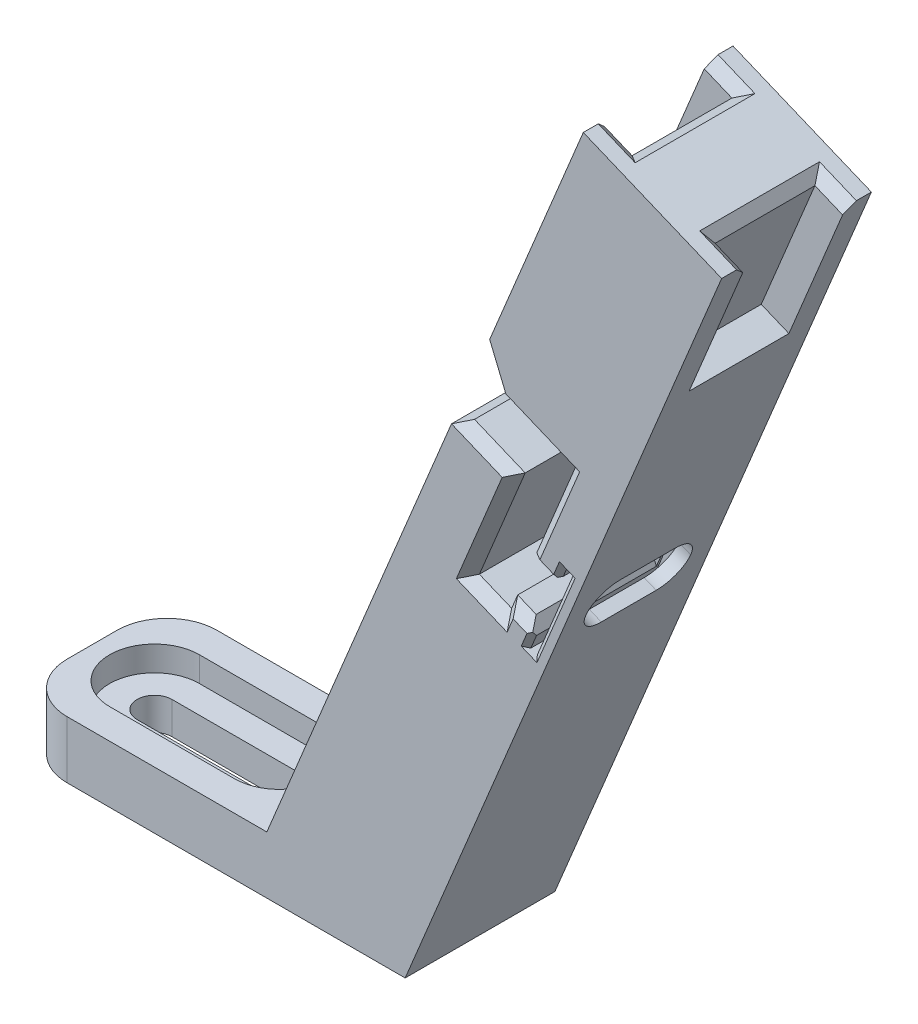
SolidWorks part; units mm, degrees
ref_plane "Front Plane" through (0, 0, 0) normal (0, 0, 1) x (1, 0, 0)
ref_plane "Top Plane" through (0, 0, 0) normal (0, 1, 0) x (1, 0, 0)
ref_plane "Right Plane" through (0, 0, 0) normal (1, 0, 0) x (0, 0, -1)
sketch "Sketch1" plane through (0, 0, 0) normal (0, 0, 1) x (1, 0, 0)
  line L7 (0, 216.4784) -> (-153.0734, 153.0734)
  line L8 (-153.0734, 153.0734) -> (-216.4784, 0)
  line L10 (0, 248.9502) -> (-176.0344, 176.0344)
  line L11 (-176.0344, 176.0344) -> (-244.1948, 11.4805)
  line L12 (0, 248.9502) -> (0, 216.4784)
  line L14 (-244.1948, 11.4805) -> (-244.1948, 0)
  line L15 (-244.1948, 0) -> (-216.4784, 0)
  line L18 (0, 0) -> (-212.4923, 88.0172) construction
  line L20 (0, 0) -> (-88.0172, 212.4923) construction
  line L27 (0, 248.9502) -> (-176.0344, 176.0344) construction
  line L28 (0, 216.4784) -> (-153.0734, 153.0734) construction
  line L29 (153.0734, 153.0734) -> (0, 216.4784) construction
  line L30 (176.0344, 176.0344) -> (0, 248.9502) construction
  line L31 (153.0734, 153.0734) -> (76.5367, 184.7759) [skipped]
  line L32 (216.4784, 0) -> (153.0734, 153.0734) construction
  line L33 (244.1948, 11.4805) -> (176.0344, 176.0344) construction
  line L34 (216.4784, 0) -> (184.7759, 76.5367) [skipped]
  line L35 (153.0734, -153.0734) -> (184.7759, -76.5367) [skipped]
  line L36 (0, -216.4784) -> (76.5367, -184.7759) [skipped]
  line L37 (-153.0734, -153.0734) -> (-76.5367, -184.7759) [skipped]
  line L38 (-216.4784, 0) -> (-184.7759, -76.5367) [skipped]
  dimension "D3" = 30
  dimension "D2" = 30
extrude "Boss-Extrude1" add sketch "Sketch1" along normal blind 30
sketch "Sketch3" plane through (0, 0, 30) normal (0, 0, 1) x (1, 0, 0)
  line L0 (-176.0344, 176.0344) -> (-153.0734, 153.0734) construction
  line L1 (0, 232.7143) -> (-164.5539, 164.5539) construction
  line L2 (0, 216.4784) -> (0, 248.9502) construction
  line L3 (-244.1948, 11.4805) -> (-216.4784, 0) construction
  line L4 (-164.5539, 164.5539) -> (-230.3366, 5.7403) construction
  line L5 (-82.2769, 198.6341) -> (-76.5367, 184.7759) construction
  line L6 (-153.0734, 153.0734) -> (0, 216.4784) construction
  line L7 (-186.6893, 71.9173) -> (-182.8625, 81.1561)
  line L8 (-184.7759, 76.5367) -> (-198.6341, 82.2769) construction
  line L9 (-216.4784, 0) -> (-153.0734, 153.0734) construction
  line L10 (-182.8625, 81.1561) -> (-192.1013, 84.9829)
  line L12 (-195.9281, 75.7441) -> (-186.6893, 71.9173)
  line L13 (-81.1561, 182.8625) -> (-71.9173, 186.6893)
  line L14 (-71.9173, 186.6893) -> (-75.7441, 195.9281)
  line L16 (-84.9829, 192.1013) -> (-81.1561, 182.8625)
  line L17 (-75.7441, 195.9281) -> (-72.8154, 197.1412)
  line L18 (-72.8154, 197.1412) -> (-75.4942, 203.6084)
  line L19 (-75.4942, 203.6084) -> (-97.6673, 194.424)
  line L20 (-106.9061, 190.5971) -> (-104.2273, 184.13)
  line L21 (-104.2273, 184.13) -> (-84.9829, 192.1013)
  line L22 (-106.9061, 190.5971) -> (-111.881, 202.6076)
  line L23 (0, 248.9502) -> (-176.0344, 176.0344) construction
  line L24 (-97.6673, 194.424) -> (-102.6422, 206.4344)
  line L25 (-102.6422, 206.4344) -> (-111.881, 202.6076)
  line L26 (-192.1013, 84.9829) -> (-184.13, 104.2273)
  line L27 (-184.13, 104.2273) -> (-202.6076, 111.881)
  line L28 (-176.0344, 176.0344) -> (-244.1948, 11.4805) construction
  line L29 (-202.6076, 111.881) -> (-206.4344, 102.6422)
  line L30 (-206.4344, 102.6422) -> (-194.424, 97.6673)
  line L31 (-194.424, 97.6673) -> (-203.6084, 75.4942)
  line L32 (-203.6084, 75.4942) -> (-197.1412, 72.8154)
  line L33 (-197.1412, 72.8154) -> (-195.9281, 75.7441)
  point P24 (-184.7759, 76.5367)
  dimension "D1" = 5
  dimension "D2" = 5
  dimension "D3" = 10
  dimension "D4" = 5
  dimension "D5" = 5
  dimension "D6" = 10
  dimension "D7" = 3.17
  dimension "D8" = 7
  dimension "D9" = 34
  dimension "D10" = 10
  dimension "D11" = 3.17
  dimension "D12" = 34
  dimension "D13" = 7
  dimension "D14" = 10
  dimension "D15" = 10
  dimension "D16" = 10
sketch "Sketch4" plane through (-244.1948, 0, 0) normal (-1, 0, 0) x (0, 0, 1)
  line L1 (0, 0) -> (30, 0)
  line L2 (0, 0) -> (0, 11.4805)
  line L3 (0, 11.4805) -> (30, 11.4805)
  line L4 (30, 0) -> (30, 11.4805)
extrude "Boss-Extrude2" add sketch "Sketch4" along normal blind 50
sketch "Sketch5" plane through (0, 11.4805, 0) normal (0, 1, 0) x (1, 0, 0)
  line L0 (-244.1948, -15) -> (-294.1948, -15) construction
  line L1 (-244.1948, -30) -> (-244.1948, 0) construction
  line L2 (-294.1948, -30) -> (-294.1948, 0) construction
  line L3 (-269.1948, -15) -> (-269.1948, 0) construction
  line L4 (-294.1948, 0) -> (-244.1948, 0) construction
  line L5 (-281.6948, -7.5) -> (-294.1948, -7.5) construction
  line L6 (-281.6948, -7.5) -> (-281.6948, -30) construction
  line L7 (-294.1948, -30) -> (-244.1948, -30) construction
  line L8 (-256.6948, -7.5) -> (-244.1948, -7.5) construction
  line L9 (-256.6948, -7.5) -> (-256.6948, -30) construction
  line L12 (-281.6948, -6) -> (-256.6948, -6)
  line L13 (-281.6948, -24) -> (-256.6948, -24)
  arc A2 (-256.6948, -24) -> (-256.6948, -6) centre (-256.6948, -15) ccw
  arc A3 (-281.6948, -6) -> (-281.6948, -24) centre (-281.6948, -15) ccw
extrude "Cut-Extrude1" cut sketch "Sketch5" against normal blind 5
sketch "Sketch7" plane through (0, 6.4805, 0) normal (0, 1, 0) x (1, 0, 0)
  line L0 (-256.6948, -11.5) -> (-281.6948, -11.5)
  line L1 (-256.6948, -6) -> (-256.6948, -24) construction
  line L2 (-256.6948, -18.5) -> (-281.6948, -18.5)
  arc A1 (-256.6948, -24) -> (-256.6948, -6) centre (-256.6948, -15) ccw construction
  arc A2 (-256.6948, -18.5) -> (-256.6948, -11.5) centre (-256.6948, -15) ccw
  arc A3 (-281.6948, -11.5) -> (-281.6948, -18.5) centre (-281.6948, -15) ccw
  dimension "D1" = 7
extrude "Cut-Extrude3" cut sketch "Sketch7" against normal up to surface (6.4805 mm away) up to face at (-255.3366, 0, 15)
fillet "Fillet1" radius 10 2 edges at (-294.1948, 5.7403, 0) (-294.1948, 5.7403, 30)
chamfer "Chamfer3" distance 22.5 angle 22.5 1 edges at (0, 248.9502, 15) first distance on face at (-88.0172, 212.4923, 15)
chamfer "Chamfer1" distance 15 angle 54 1 edges at (0, 228.4091, 0) first distance on face at (0, 228.4091, 15)
chamfer "Chamfer2" distance 15 angle 54 1 edges at (0, 228.4091, 30) first distance on face at (0, 228.4091, 22.5)
extrude "Cut-Extrude4" cut sketch "Sketch3" against normal blind 25
sketch "Sketch8" plane through (0, 0, 30) normal (0, 0, 1) x (1, 0, 0)
  line L0 (-20.6457, 224.1333) -> (-173.822, 160.6856) construction
  line L1 (-20.6457, 207.9267) -> (-20.6457, 240.3398) construction
  line L2 (-66.2826, 194.4352) -> (-67.8133, 198.1308)
  line L3 (-73.1709, 211.0651) -> (-72.247, 211.4478)
  line L5 (-74.9258, 217.9149) -> (-46.2856, 229.7781)
  line L6 (-38.9874, 225.2244) -> (-37.4566, 221.5288)
  line L8 (-66.2826, 194.4352) -> (-32.0991, 208.5945)
  line L9 (-72.8154, 197.1412) -> (-75.4942, 203.6084) construction
  line L10 (-71.9173, 186.6893) -> (-20.6457, 207.9267) construction
  line L11 (-67.8133, 198.1308) -> (-66.8895, 198.5134)
  line L12 (-66.8895, 198.5134) -> (-70.7163, 207.7522)
  line L13 (-70.7163, 207.7522) -> (-71.6402, 207.3696)
  line L14 (-33.6298, 212.2901) -> (-38.2492, 210.3766)
  line L15 (-38.2492, 210.3766) -> (-42.076, 219.6154)
  line L16 (-42.076, 219.6154) -> (-37.4566, 221.5288)
  line L17 (-33.6298, 212.2901) -> (-32.0991, 208.5945)
  line L18 (-71.6402, 207.3696) -> (-73.1709, 211.0651)
  line L19 (-38.9874, 225.2244) -> (-43.6068, 223.3109)
  line L20 (-43.6068, 223.3109) -> (-46.2856, 229.7781)
  line L21 (-72.247, 211.4478) -> (-74.9258, 217.9149)
  dimension "D1" = 37
  dimension "D2" = 5
  dimension "D3" = 5
  dimension "D4" = 4
  dimension "D5" = 10
  dimension "D6" = 1
  dimension "D7" = 4
  dimension "D8" = 10
  dimension "D9" = 5
  dimension "D10" = 5
  dimension "D11" = 4
  dimension "D12" = 4
  dimension "D13" = 1
extrude "Cut-Extrude5" cut sketch "Sketch8" against normal blind 25
sketch "Sketch9" plane through (0, 240.3398, 0) normal (0, 1, 0) x (1, 0, 0)
  line L1 (-20.6457, -30) -> (0, -30)
  line L2 (-20.6457, -30) -> (-20.6457, 0)
  line L3 (-20.6457, 0) -> (0, 0)
  line L4 (0, -30) -> (0, 0)
extrude "Cut-Extrude6" cut sketch "Sketch9" against normal blind 40 body kept at (-20.7873, 240.3398, 30)
sketch "Sketch10" plane through (-20.6457, 0, 0) normal (1, 0, 0) x (0, 0, -1)
  line L8 (-10, 217.9267) -> (-10, 230.3398)
  line L9 (-10, 230.3398) -> (-20, 230.3398)
  line L10 (-20, 230.3398) -> (-20, 217.9267)
  line L11 (-20, 217.9267) -> (-10, 217.9267)
  line L12 (-10, 217.9267) -> (-10, 230.3398)
  line L13 (-10, 230.3398) -> (-20, 230.3398)
  line L14 (-20, 230.3398) -> (-20, 217.9267)
  line L15 (-20, 217.9267) -> (-10, 217.9267)
  dimension "D1" = 10
extrude "Boss-Extrude3" add sketch "Sketch10" along normal blind 12
sketch "Sketch11" plane through (-76.5367, 184.7759, 0) normal (0.3827, -0.9239, 0) x (0.9239, 0.3827, 0)
  line L0 (-82.8427, 30) -> (-5, 30) construction
  line L1 (-15, 30) -> (16, 30)
  line L2 (-15, 30) -> (-15, 0)
  line L3 (-15, 0) -> (16, 0)
  line L4 (16, 30) -> (16, 0)
  line L5 (-82.8427, 0) -> (60.4959, 0) construction
  line L6 (-5, 5) -> (-5, 30) construction
  line L7 (5, 5) -> (5, 30) construction
  dimension "D1" = 10
  dimension "D2" = 11
  dimension "D3" = 30
  dimension "D4" = 31
extrude "Cut-Extrude7" cut sketch "Sketch11" against normal blind 2
sketch "Sketch12" plane through (-184.7759, 76.5367, 0) normal (0.9239, -0.3827, 0) x (0, 0, -1)
  line L0 (-4.5, -10) -> (-4.5, 10)
  line L1 (-30, -10) -> (-4.5, -10)
  line L3 (-30, 10) -> (-4.5, 10)
  line L6 (-5, -5) -> (-30, -5) construction
  line L7 (-5, 5) -> (-30, 5) construction
  line L8 (-30, -10) -> (-30, 10)
  line L9 (-30, 5) -> (-30, 82.8427) construction
  dimension "D1" = 5
  dimension "D2" = 5
  dimension "D3" = 0
extrude "Cut-Extrude8" cut sketch "Sketch12" against normal blind 4
chamfer "Chamfer4" distance 2 angle 45 29 edges at (-40.1626, 214.996, 30) (-72.4055, 209.2173, 30) (-38.222, 223.3766, 30) (-67.048, 196.283, 30) (-32.8644, 210.4423, 30) (-49.1908, 201.5149, 30) (-81.9215, 184.7102, 17.5) (-108.0542, 193.3688, 30) (-83.4522, 188.4058, 30) (-94.6051, 188.1156, 30) (-72.6827, 188.5371, 17.5) (-100.1548, 200.4292, 30) (-74.2134, 192.2326, 30) (-74.2798, 196.5347, 30) (-74.1548, 200.3748, 30) (-86.5808, 199.0162, 30) (-190.3848, 73.448, 17.5) (-193.1565, 74.5961, 30) (-196.5347, 74.2798, 30) (-200.3748, 74.1548, 30) (-199.0162, 86.5808, 30) (-200.4292, 100.1548, 30) (-186.558, 82.6868, 17.5) (-189.3296, 83.8349, 30) (-188.1156, 94.6051, 30) (-193.3688, 108.0542, 30) (-111.881, 202.6076, 17.5) (-102.6422, 206.4344, 17.5) (-206.4344, 102.6422, 17.5)
sketch "Sketch13" plane through (0, 0, 0) normal (0, 0, -1) x (-1, 0, 0)
  line L0 (157.1443, 143.2452) -> (184.8607, 154.7257) construction
  line L1 (216.4784, 0) -> (153.0734, 153.0734) construction
  line L2 (176.0344, 176.0344) -> (244.1948, 11.4805) construction
  line L3 (153.0734, 153.0734) -> (180.7898, 164.5539) construction
  line L7 (180.7898, 164.5539) -> (153.0734, 153.0734)
  line L9 (153.0734, 153.0734) -> (-25.4339, 226.4245)
  line L10 (-25.4339, 226.4245) -> (-10.4166, 262.9705)
  line L11 (-10.4166, 262.9705) -> (187.5273, 181.6326)
  line L12 (187.5273, 181.6326) -> (180.7898, 164.5539)
extrude "Cut-Extrude9" cut sketch "Sketch13" against normal blind 30
sketch "Sketch16" plane through (31.7025, 76.5367, 0) normal (0.3827, 0.9239, 0) x (0.9239, -0.3827, 0)
  line L4 (-230, -30) -> (-230, 0) construction
  line L5 (-230, -25) -> (-224, -25)
  line L6 (-230, -25) -> (-230, -5)
  line L7 (-230, -5) -> (-224, -5)
  line L8 (-224, -25) -> (-224, -5)
  line L9 (-200, -30) -> (-200, 0) construction
  line L10 (-200, -25) -> (-206, -25)
  line L11 (-200, -25) -> (-200, -5)
  line L16 (-200, -5) -> (-206, -5)
  line L17 (-206, -25) -> (-206, -5)
  line L18 (-200, 0) -> (-230, 0) construction
  line L19 (-200, -30) -> (-230, -30) construction
  dimension "D1" = 5
  dimension "D2" = 5
  dimension "D3" = 6
  dimension "D4" = 6
extrude "Cut-Extrude10" cut sketch "Sketch16" against normal blind 30.1
chamfer "Chamfer6" distance 2 angle 45 6 edges at (-178.0181, 163.4058, 25) (-178.0181, 163.4058, 5) (-175.2465, 162.2578, 15) (-155.845, 154.2214, 5) (-155.845, 154.2214, 25) (-158.6167, 155.3695, 15)
sketch "Sketch17" plane through (0, 0, 4.5) normal (0, 0, 1) x (1, 0, 0)
  line L0 (-188.6027, 67.2979) -> (-191.0048, 68.2929)
  line L1 (-192.2983, 68.8286) -> (-188.6027, 67.2979) construction
  line L2 (-191.0048, 68.2929) -> (-189.0914, 72.9123)
  line L3 (-184.6446, 87.3062) -> (-180.9491, 85.7755) construction
  line L4 (-183.3512, 86.7705) -> (-180.9491, 85.7755)
  line L5 (-180.9491, 85.7755) -> (-182.8625, 81.1561)
  line L6 (-192.2983, 68.8286) -> (-184.6446, 87.3062) construction
  line L7 (-189.0914, 72.9123) -> (-186.6893, 71.9173)
  line L8 (-185.2646, 82.1511) -> (-182.8625, 81.1561)
  line L9 (-186.6893, 71.9173) -> (-188.6027, 67.2979)
  line L10 (-185.2646, 82.1511) -> (-183.3512, 86.7705)
  dimension "D1" = 1.4
  dimension "D2" = 5
  dimension "D3" = 5
extrude "Boss-Extrude4" add sketch "Sketch17" along normal up to surface (25.5 mm away) up to face at (-216.8731, 53.8177, 30)
sketch "Sketch18" plane through (-1.9134, -4.6194, 0) normal (0.3827, 0.9239, 0) x (0.9239, -0.3827, 0)
  line L0 (-200, -30) -> (-200, -4.5) construction
  line L1 (-202.6, -30) -> (-200, -30)
  line L2 (-202.6, -30) -> (-202.6, -25.5)
  line L3 (-202.6, -25.5) -> (-200, -25.5)
  line L4 (-200, -30) -> (-200, -25.5)
  dimension "D1" = 4.5
extrude "Boss-Extrude5" add sketch "Sketch18" along normal up to surface (10 mm away) up to face at (-184.0635, 81.6536, 17.25)
chamfer "Chamfer7" distance 1 angle 45 3 edges at (-185.2186, 85.9204, 30) (-187.178, 77.5317, 30) (-191.7242, 70.2144, 30)
fillet "Fillet2" radius 5 4 edges at (-187.8904, 72.4148, 25.5) (-184.0635, 81.6536, 25.5) (-184.0635, 81.6536, 4.5) (-187.8904, 72.4148, 4.5)
chamfer "Chamfer8" distance 8 angle 45 1 edges at (-202.6076, 111.881, 16.5)
